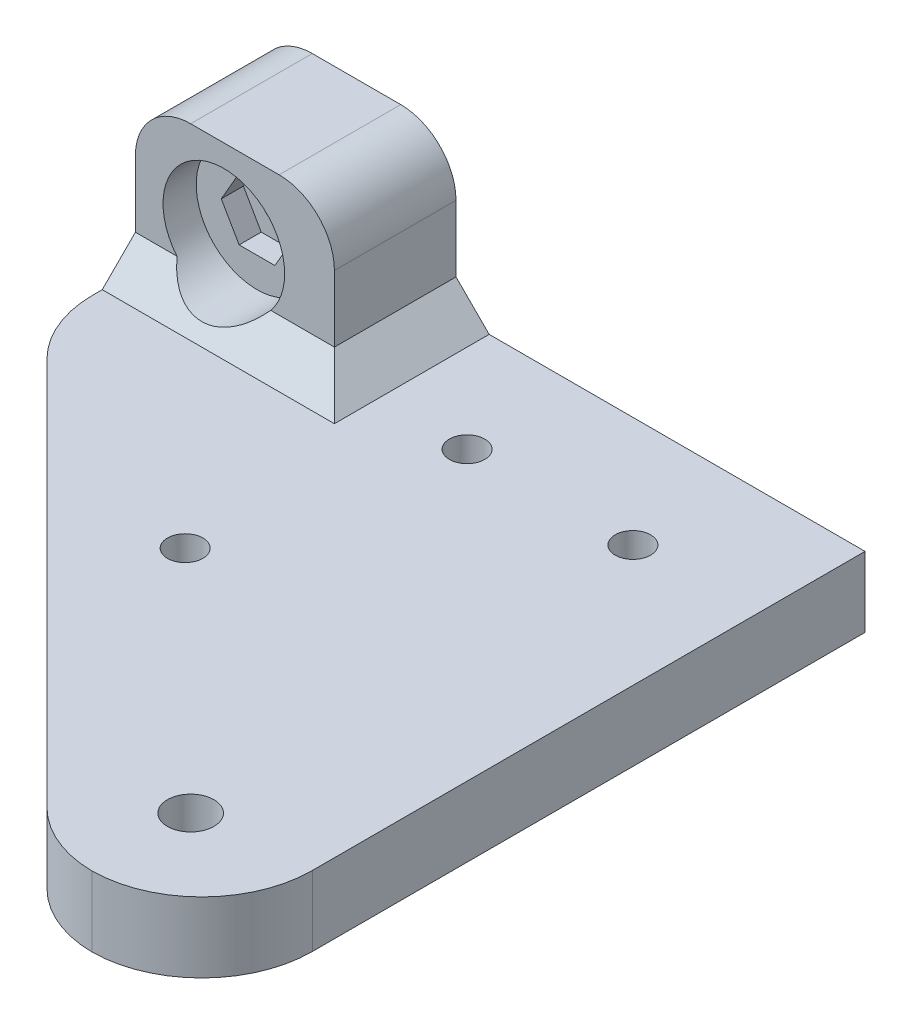
SolidWorks part; units mm, degrees
ref_plane "Front Plane" through (0, 0, 0) normal (0, 0, 1) x (1, 0, 0)
ref_plane "Top Plane" through (0, 0, 0) normal (0, 1, 0) x (1, 0, 0)
ref_plane "Right Plane" through (0, 0, 0) normal (1, 0, 0) x (0, 0, -1)
sketch "Sketch1" plane through (251.8861, -2636.0305, -0.2779) normal (0, 1, 0) x (1, 0, 0)
  line L0 (-265.8861, -0.2779) -> (-251.8861, -0.2779)
  line L1 (-251.8861, -0.2779) -> (-251.8861, 59.7221)
  line L2 (-251.8861, 59.7221) -> (-306.8861, 59.7221)
  line L3 (-306.8861, 59.7221) -> (-306.8861, 40.7221)
  line L4 (-306.8861, 40.7221) -> (-265.8861, -0.2779)
  line L5 (-262.8861, 49.7221) -> (-277.8861, 49.7221) construction
  circle A0 centre (-261.8861, 8.7221) radius 2.1
  circle A1 centre (-282.8861, 29.2221) radius 1.6
  circle A2 centre (-262.8861, 49.7221) radius 1.6
  circle A3 centre (-277.8861, 49.7221) radius 1.6
  dimension "D5" = 4.2
  dimension "D6" = 3.2
  dimension "D12" = 3.2
  dimension "D13" = 3.2
  dimension "D2" = 55
  dimension "D3" = 41
  dimension "D4" = 60
  dimension "D7" = 10
  dimension "D8" = 31
  dimension "D9" = 9
  dimension "D10" = 29.5
  dimension "D11" = 45
  dimension "D14" = 15
  dimension "D15" = 10
  dimension "D16" = 11
extrude "Boss-Extrude1" add sketch "Sketch1" along normal blind 6.35
ref_plane "Plane1" through (-55, -2629.6805, -60) normal (0, -1, 0) x (-1, 0, 0)
sketch "Sketch2" plane through (-55, -2629.6805, -60) normal (0, -1, 0) x (1, 0, 0)
  line L1 (0, 0) -> (18, 0)
  line L2 (0, 0) -> (0, 11)
  line L3 (0, 11) -> (18, 11)
  line L4 (18, 0) -> (18, 11)
  dimension "D1" = 11
  dimension "D2" = 18
extrude "Boss-Extrude2" add sketch "Sketch2" against normal blind 14
sketch "Sketch3" plane through (0, 0, -49) normal (0, 0, 1) x (1, 0, 0)
  line L0 (-37, -2629.6805) -> (-55, -2629.6805) construction
  line L3 (-55, -2615.6805) -> (-55, -2629.6805) construction
  circle A0 centre (-47, -2623.1805) radius 5.5
  dimension "D1" = 11
  dimension "D2" = 6.5
  dimension "D3" = 8
extrude "Cut-Extrude1" cut sketch "Sketch3" against normal blind 3
chamfer "Chamfer1" distance 3 angle 45 2 edges
fillet "Fillet2" radius 10 3 edges at (-14, -2632.8555, 0) (-55, -2632.8555, -41) (0, -2632.8555, 0)
fillet "Fillet3" radius 5 2 edges at (-37, -2615.6805, -54.5) (-55, -2615.6805, -54.5)
sketch "Sketch4" plane through (0, 0, -52) normal (0, 0, 1) x (1, 0, 0)
  line L1 (-45.3834, -2625.9805) -> (-43.7668, -2623.1805)
  line L2 (-43.7668, -2623.1805) -> (-45.3834, -2620.3805)
  line L3 (-45.3834, -2620.3805) -> (-48.6166, -2620.3805)
  line L4 (-48.6166, -2620.3805) -> (-50.2332, -2623.1805)
  line L5 (-50.2332, -2623.1805) -> (-48.6166, -2625.9805)
  line L6 (-48.6166, -2625.9805) -> (-45.3834, -2625.9805)
  circle A0 centre (-47, -2623.1805) radius 2.8 construction
  dimension "D1" = 5.6
extrude "Cut-Extrude2" cut sketch "Sketch4" against normal blind 2
sketch "Sketch5" plane through (0, 0, -54) normal (0, 0, 1) x (1, 0, 0)
  circle A0 centre (-47, -2623.1805) radius 1.6
  dimension "D1" = 3.2
extrude "Cut-Extrude3" cut sketch "Sketch5" against normal through all
sketch "Sketch6" plane through (0, 0, -60) normal (0, 0, -1) x (-1, 0, 0)
  circle A0 centre (47, -2623.1805) radius 2.95
  dimension "D1" = 5.9
extrude "Cut-Extrude4" cut sketch "Sketch6" against normal blind 3
